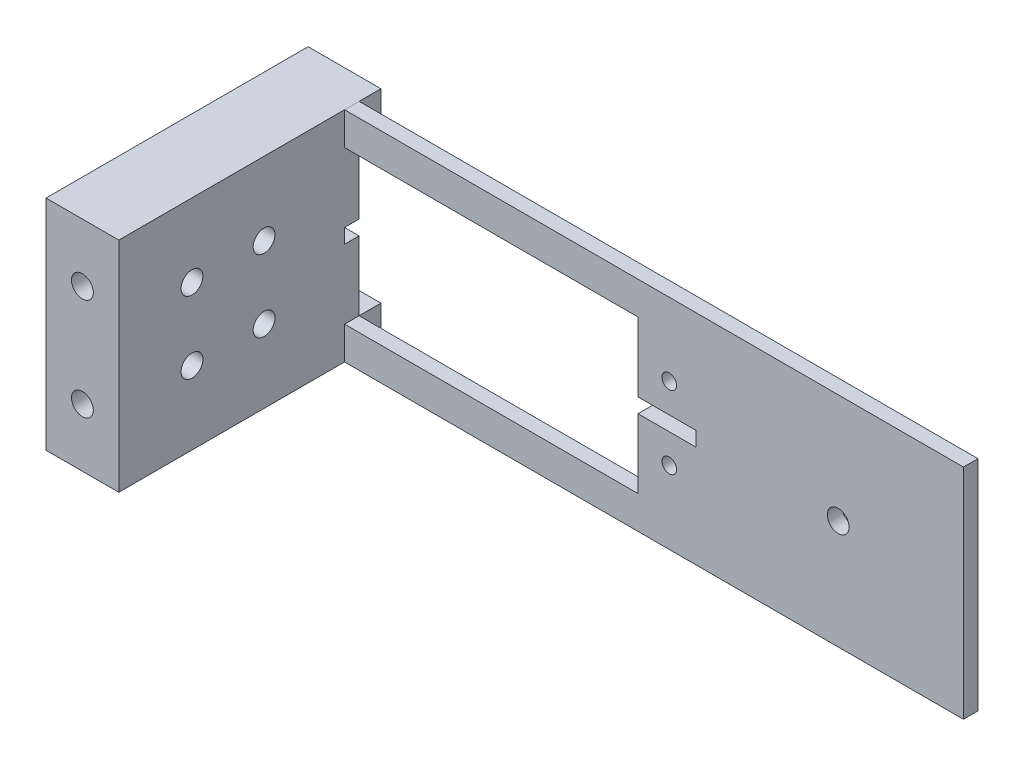
SolidWorks part; units mm, degrees
ref_plane "Спереди" through (0, 0, 0) normal (0, 0, 1) x (1, 0, 0)
ref_plane "Сверху" through (0, 0, 0) normal (0, 1, 0) x (1, 0, 0)
ref_plane "Справа" through (0, 0, 0) normal (1, 0, 0) x (0, 0, -1)
sketch "Эскиз1" plane through (0, 0, 0) normal (0, 1, 0) x (1, 0, 0)
  line L0 (10, 0) -> (10, 31)
  line L1 (0, 0) -> (10, 0)
  line L2 (0, 0) -> (0, 36)
  line L3 (0, 36) -> (10, 36)
  line L4 (10, 0) -> (9.7456, 0.0582)
  line L5 (10, 31) -> (95, 31)
  line L6 (95, 31) -> (95, 33)
  line L7 (95, 33) -> (10, 33)
  line L8 (10, 33) -> (10, 36)
  dimension "D1" = 36
  dimension "D2" = 3
  dimension "D3" = 10
  dimension "D4" = 31
extrude "Бобышка-Вытянуть1" add sketch "Эскиз1" along normal blind 30 contours L5 L6 L3 L2 L1 L0 region at (5, 0, -1.0159)
sketch "Эскиз2" plane through (0, 0, 0) normal (-1, 0, 0) x (0, 0, 1)
  line L0 (-15, 22) -> (-22, 15) construction
  line L1 (-18.5, 18.5) -> (-19.9497, 19.9497) construction
  line L2 (-18.5, 18.5) -> (-10.0503, 10.0503) construction
  line L3 (0, 30) -> (0, 0) construction
  line L4 (0, 0) -> (-36, 0) construction
  line L5 (-15, 15) -> (-10.0503, 19.9497) construction
  line L6 (-15, 15) -> (-19.9497, 10.0503) construction
  circle A0 centre (-15, 15) radius 7 construction
  circle A1 centre (-19.9497, 19.9497) radius 1.5
  circle A2 centre (-10.0503, 19.9497) radius 1.5
  circle A3 centre (-19.9497, 10.0503) radius 1.5
  circle A4 centre (-10.0503, 10.0503) radius 1.5
  circle A5 centre (-15, 15) radius 8.5 construction
  dimension "D1" = 14
  dimension "D4" = 17
  dimension "D2" = 15
  dimension "D3" = 15
extrude "Вырез-Вытянуть1" cut sketch "Эскиз2" against normal through all
sketch "Эскиз3" plane through (0, 0, -36) normal (0, 0, -1) x (-1, 0, 0)
  line L1 (-10, 25.5) -> (-50.3, 25.5)
  line L2 (-10, 25.5) -> (-10, 4.5)
  line L3 (-10, 4.5) -> (-50.3, 4.5)
  line L4 (-50.3, 25.5) -> (-50.3, 4.5)
  line L5 (0, 30) -> (0, 0) construction
  point P4 (-10, 15)
  point P5 (0, 15)
  dimension "D1" = 21
  dimension "D3" = 10
  dimension "D4" = 40.3
extrude "Вырез-Вытянуть2" cut sketch "Эскиз3" against normal through all
sketch "Эскиз4" plane through (0, 0, -36) normal (0, 0, -1) x (-1, 0, 0)
  line L5 (-10, 4.5) -> (-2, 4.5)
  line L6 (-10, 4.5) -> (-10, 25.5)
  line L7 (-10, 25.5) -> (-2, 25.5)
  line L8 (-2, 4.5) -> (-2, 25.5)
  line L9 (-10, 25.5) -> (-50.3, 25.5) construction
  point P0 (0, 0)
  dimension "D2" = 8
extrude "Вырез-Вытянуть3" cut sketch "Эскиз4" against normal blind 3
sketch "Эскиз5" plane through (0, 0, -36) normal (0, 0, -1) x (-1, 0, 0)
  line L0 (-2, 4.5) -> (-2, 25.5) construction
  line L1 (-58.3, 16) -> (-2, 16)
  line L2 (-58.3, 14) -> (-2, 14)
  line L4 (-2, 16) -> (-2, 14)
  line L8 (-2, 16) -> (-58.3, 16) construction
  line L9 (-58.3, 14) -> (-58.3, 16)
  line L15 (-2, 14) -> (-58.3, 14) construction
  point P8 (-2, 15)
  point P12 (-2, 15)
  dimension "D1" = 56.3
  dimension "D2" = 2
extrude "Вырез-Вытянуть4" cut sketch "Эскиз5" against normal blind 5
sketch "Эскиз6" plane through (0, 0, -33) normal (0, 0, -1) x (-1, 0, 0)
  line L1 (-10, 16) -> (-10, 14) construction
  line L2 (-5.4, 10) -> (-5.4, 20) construction
  line L3 (-5.4, 10) -> (-54.6, 10) construction
  line L4 (-10, 30) -> (-10, 25.5) construction
  line L5 (-5.4, 11) -> (-54.6, 11) construction
  line L6 (-4.4, 10) -> (-4.4, 22.6602) construction
  line L7 (-5.4, 20) -> (-54.6, 20) construction
  line L8 (-5.4, 21) -> (-54.6, 21) construction
  line L9 (-54.6, 10) -> (-54.6, 21) construction
  circle A0 centre (-5.4, 10) radius 1
  circle A1 centre (-54.6, 10) radius 1
  circle A2 centre (-5.4, 20) radius 1
  circle A3 centre (-54.6, 20) radius 1
  point P6 (-10, 15)
  dimension "D1" = 4.6
  dimension "D3" = 2
  dimension "D4" = 49.2
  dimension "D5" = 10
  dimension "D2" = 5
extrude "Вырез-Вытянуть5" cut sketch "Эскиз6" against normal blind 4
sketch "Эскиз7" plane through (0, 0, -36) normal (0, 0, -1) x (-1, 0, 0)
  line L0 (-95, 30) -> (-95, 0) construction
  line L1 (-77.8, 15) -> (-95, 15) construction
  line L4 (-50.3, 4.5) -> (-50.3, 14) construction
  circle A0 centre (-77.8, 15) radius 1.5
  dimension "D1" = 27.5
  dimension "D2" = 3
extrude "Вырез-Вытянуть6" cut sketch "Эскиз7" against normal through all
sketch "Эскиз8" plane through (0, 0, 0) normal (0, 0, 1) x (1, 0, 0)
  line L0 (5, 30) -> (5, 0) construction
  line L1 (0, 30) -> (10, 30) construction
  line L2 (0, 0) -> (10, 0) construction
  line L3 (3.5, 22) -> (3.5, 8) construction
  circle A0 centre (5, 22) radius 1.5
  circle A1 centre (5, 8) radius 1.5
  point P12 (0, 0)
  point P13 (0, 0)
  dimension "D1" = 3
  dimension "D2" = 8
  dimension "D3" = 14
extrude "Вырез-Вытянуть7" cut sketch "Эскиз8" against normal blind 4
split "Разделить1" bodies to split 113 resulting bodies 111 112 split by face at (10, 15, -26.5)
